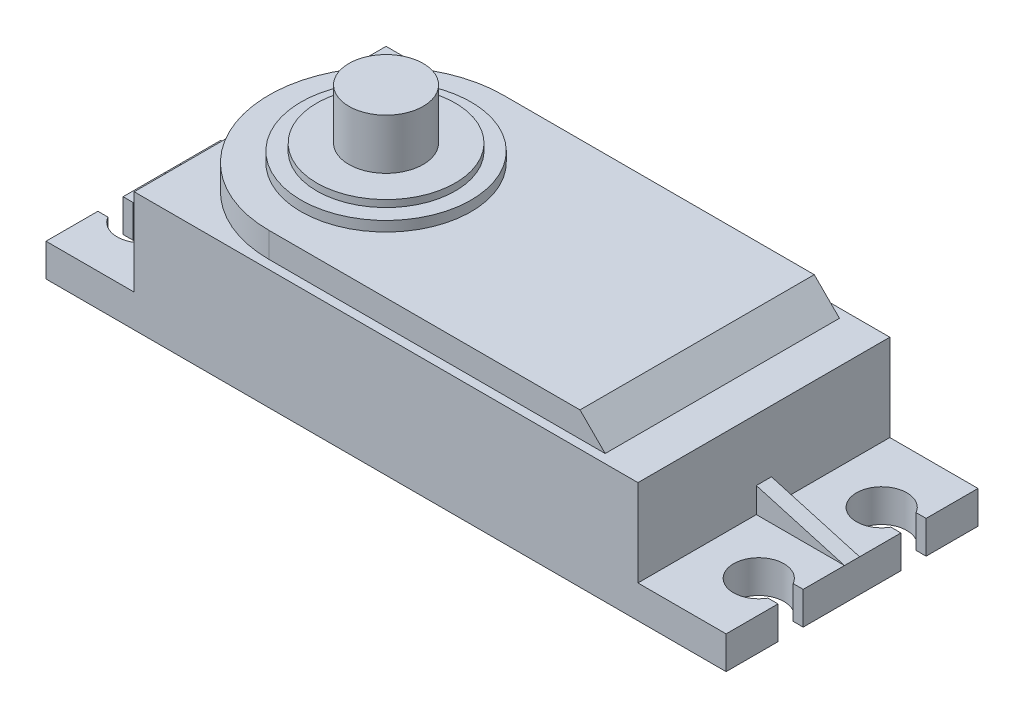
SolidWorks part; units mm, degrees
ref_plane "Alzado" through (0, 0, 0) normal (0, 0, 1) x (1, 0, 0)
ref_plane "Planta" through (0, 0, 0) normal (0, 1, 0) x (1, 0, 0)
ref_plane "Vista lateral" through (0, 0, 0) normal (1, 0, 0) x (0, 0, -1)
sketch "Croquis base" plane through (0, 0, 0) normal (0, 1, 0) x (1, 0, 0)
  line L1 (-27, 10) -> (27, 10)
  line L2 (-27, 10) -> (-27, -10)
  line L3 (-27, -10) -> (27, -10)
  line L4 (27, 10) -> (27, -10)
  line L5 (-27, 10) -> (27, -10) construction
  line L6 (-27, -10) -> (27, 10) construction
  point P0 (0, 0)
  dimension "D1" = 54
  dimension "D2" = 20
extrude "Saliente-Extruir1" add sketch "Croquis base" along normal blind 2.6
sketch "Croquis step 2" plane through (0, 2.6, 0) normal (0, 1, 0) x (1, 0, 0)
  line L0 (-27, -10) -> (27, -10) construction
  line L1 (-20, 10) -> (20, 10)
  line L2 (-20, 10) -> (-20, -10)
  line L3 (-20, -10) -> (20, -10)
  line L4 (20, 10) -> (20, -10)
  line L5 (-20, 10) -> (20, -10) construction
  line L6 (-20, -10) -> (20, 10) construction
  line L7 (-27, 0) -> (27, 0) construction
  line L8 (-27, 10) -> (-27, -10) construction
  line L9 (27, -10) -> (27, 10) construction
  line L10 (27, 10) -> (-27, 10) construction
  line L11 (-24.472, 4.88) -> (-27, 4.88) construction
  line L12 (-27, 5.88) -> (-26.2041, 5.88)
  line L13 (-27, 5.88) -> (-26.2041, 5.88)
  line L15 (-27, 3.88) -> (-26.2041, 3.88)
  line L16 (-27, 3.88) -> (-26.2041, 3.88)
  line L17 (-24.472, -4.88) -> (-27, -4.88) construction
  line L18 (-27, -3.88) -> (-26.2041, -3.88)
  line L19 (-27, -3.88) -> (-26.2041, -3.88)
  line L20 (-27, -5.88) -> (-26.2041, -5.88)
  line L21 (-27, -5.88) -> (-26.2041, -5.88)
  line L22 (0, 10) -> (0, -10) construction
  line L23 (27, -5.88) -> (26.2041, -5.88)
  line L24 (27, -5.88) -> (26.2041, -5.88)
  line L25 (27, -3.88) -> (26.2041, -3.88)
  line L26 (27, -3.88) -> (26.2041, -3.88)
  line L27 (27, 3.88) -> (26.2041, 3.88)
  line L28 (27, 3.88) -> (26.2041, 3.88)
  line L29 (27, 5.88) -> (26.2041, 5.88)
  line L30 (27, 5.88) -> (26.2041, 5.88)
  arc A0 (-26.2041, 3.88) -> (-26.2041, 5.88) centre (-24.472, 4.88) ccw
  arc A1 (-26.2041, -3.88) -> (-26.2041, -5.88) centre (-24.472, -4.88) cw
  arc A2 (26.2041, -3.88) -> (26.2041, -5.88) centre (24.472, -4.88) ccw
  arc A3 (26.2041, 3.88) -> (26.2041, 5.88) centre (24.472, 4.88) cw
  point P0 (0, 0)
  line M8 (27, -10) -> (27, 10)
  line M9 (27, 10) -> (-27, 10)
  line M10 (-27, 10) -> (-27, -10)
  line M11 (-27, -10) -> (27, -10)
  dimension "D2" = 4
  dimension "D1" = 40
  dimension "D3" = 5.12
  dimension "D4" = 2.528
  dimension "D5" = 2
extrude "Cortar-Extruir1" cut sketch "Croquis step 2" against normal blind 2.6 contours L15 A0 L12 M10 | A1 L18 L20 M10 | A3 L27 L29 M8 | L25 A2 L23 M8 region at (-24.6695, 2.6, 4.88) region at (-24.6695, 2.6, -4.88) region at (24.6695, 2.6, -4.88) region at (24.6695, 2.6, 4.88)
extrude "Saliente-Extruir2" add sketch "Croquis step 2<3>" along normal blind 6.9 contours L4 L2 M9 M11 region at (0, 2.6, 0)
sketch "Croquis step 2<3>" plane through (0, 2.6, 0) normal (0, 1, 0) x (1, 0, 0) same geometry as "Croquis step 2"
sketch "Croquis7" plane through (0, 9.5, 0) normal (0, 1, 0) x (1, 0, 0)
  line L1 (-10, 9.3) -> (16.7, 9.3)
  line L3 (-10, -9.3) -> (16.7, -9.3)
  line L4 (16.7, 9.3) -> (16.7, -9.3)
  line L5 (-20, -10) -> (20, -10) construction
  line L7 (16.7, 0) -> (-19.3, 0) construction
  line L8 (-20, 10) -> (-20, -10) construction
  arc A0 (-10, 9.3) -> (-10, -9.3) centre (-10, 0) ccw
  dimension "D1" = 0.7
  dimension "D2" = 36
  dimension "D3" = 18.6
  dimension "D4" = 0.7
extrude "Saliente-Extruir5" add sketch "Croquis7" along normal blind 2
sketch "Croquis5" plane through (0, 2.6, 0) normal (0, 1, 0) x (1, 0, 0)
  line L7 (20, 0) -> (27, 0) construction
  line L8 (20, 10) -> (20, -10) construction
  line L9 (27, -3.88) -> (27, 3.88) construction
  line L11 (20, -0.6) -> (27, -0.6)
  line L12 (20, -0.6) -> (20, 0.6)
  line L13 (20, 0.6) -> (27, 0.6)
  line L14 (27, -0.6) -> (27, 0.6)
  dimension "D1" = 1.2
  dimension "D2" = 0.6
extrude "Saliente-Extruir6" add sketch "Croquis5" along normal blind 2
sketch "Croquis3" plane through (0, 2.6, 0) normal (0, 1, 0) x (1, 0, 0)
  line L5 (-20, -0.6) -> (-27, -0.6)
  line L6 (-20, -0.6) -> (-20, 0.6)
  line L7 (-20, 0) -> (-27, 0) construction
  line L8 (-20, 10) -> (-20, -10) construction
  line L9 (-27, 3.88) -> (-27, -3.88) construction
  line L10 (-20, 0.6) -> (-27, 0.6)
  line L11 (-27, -0.6) -> (-27, 0.6)
  dimension "D1" = 1.2
  dimension "D2" = 0.6
extrude "Saliente-Extruir7" add sketch "Croquis3" along normal blind 2
sketch "Croquis8" plane through (0, 0, 0.6) normal (0, 0, 1) x (1, 0, 0)
  line L0 (-27, 2.6) -> (-27, 4.6)
  line L1 (-27, 4.6) -> (-20, 4.6)
  line L2 (-20, 4.6) -> (-27, 2.6)
extrude "Cortar-Extruir4" cut sketch "Croquis8" against normal blind 1.2
sketch "Croquis9" plane through (0, 0, 0.6) normal (0, 0, 1) x (1, 0, 0)
  line L0 (27, 2.6) -> (20, 4.6)
  line L1 (20, 4.6) -> (27, 4.6)
  line L2 (27, 4.6) -> (27, 2.6)
extrude "Cortar-Extruir5" cut sketch "Croquis9" against normal blind 1.2
sketch "Croquis10" plane through (0, 11.5, 0) normal (0, 1, 0) x (1, 0, 0)
  circle A0 centre (-10, 0) radius 6.75
extrude "Saliente-Extruir8" add sketch "Croquis10" along normal blind 0.8
sketch "Croquis11" plane through (0, 12.3, 0) normal (0, 1, 0) x (1, 0, 0)
  circle A0 centre (-10, 0) radius 5.5
extrude "Saliente-Extruir9" add sketch "Croquis11" along normal blind 0.55
fillet "Chaflán1" radius 2 1 edges at (16.7, 11.5, 0) type face fillet profile chamfer first side face at (-10, 11.5, 6.75) second side face at (16.7, 10.5, 0)
sketch "Croquis12" plane through (0, 12.85, 0) normal (0, 1, 0) x (1, 0, 0)
  circle A0 centre (-10, 0) radius 2.95
extrude "Saliente-Extruir10" add sketch "Croquis12" along normal blind 4
